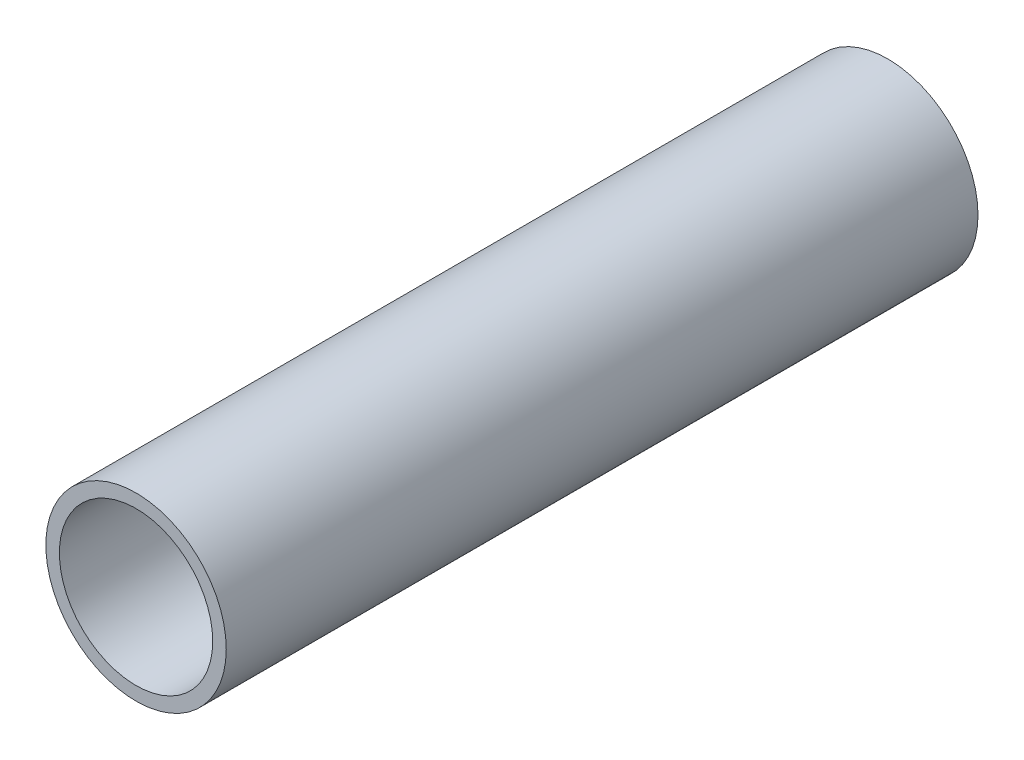
SolidWorks part; units mm, degrees
ref_plane "Front" through (0, 0, 0) normal (0, 0, 1) x (1, 0, 0)
ref_plane "Top" through (0, 0, 0) normal (0, 1, 0) x (1, 0, 0)
ref_plane "Right" through (0, 0, 0) normal (1, 0, 0) x (0, 0, -1)
sketch "Эскиз1" plane through (0, 0, 0) normal (0, 0, 1) x (1, 0, 0)
  circle A0 centre (0, 0) radius 51
  circle A1 centre (0, 0) radius 60
  dimension "D1" = 120
  dimension "D2" = 102
extrude "Бобышка-Вытянуть1" add sketch "Эскиз1" along normal blind 500
